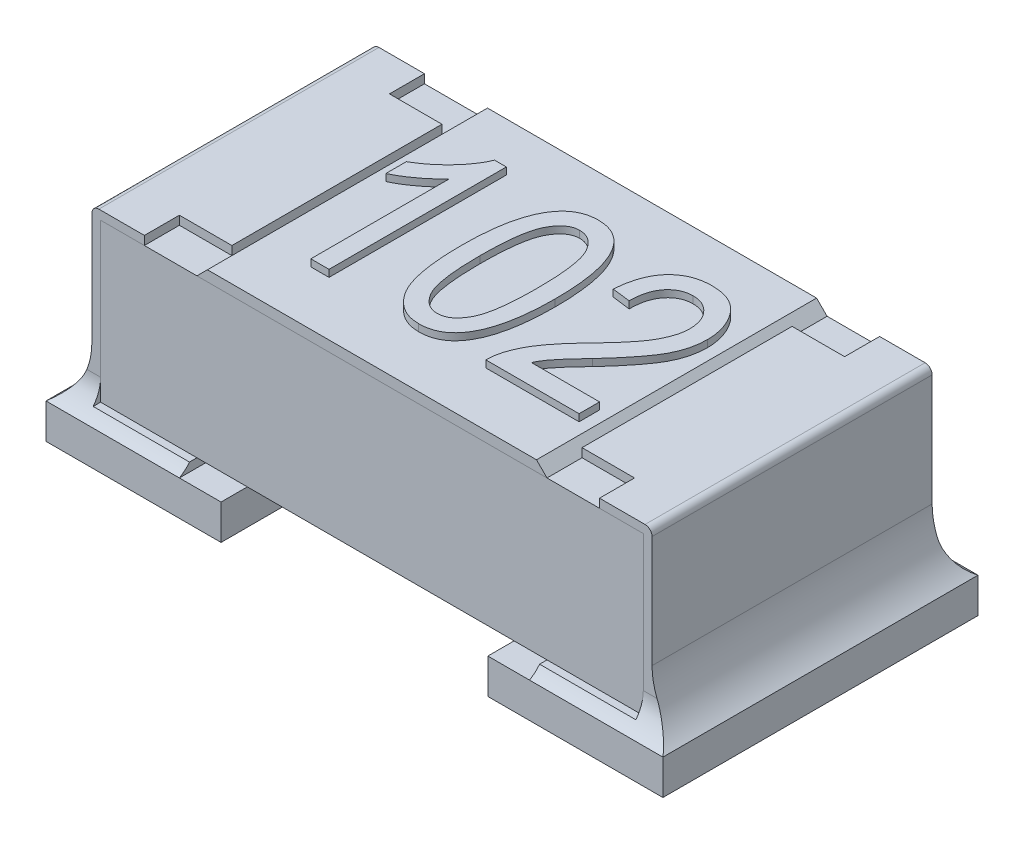
SolidWorks part; units mm, degrees
material "Ceramic Porcelain"
ref_plane "Front Plane" through (0, 0, 0) normal (0, 0, 1) x (1, 0, 0)
ref_plane "Top Plane" through (0, 0, 0) normal (0, 1, 0) x (1, 0, 0)
ref_plane "Right Plane" through (0, 0, 0) normal (1, 0, 0) x (0, 0, -1)
sketch "Sketch1" plane through (0, 0, 0) normal (1, 0, 0) x (0, 0, -1)
  line L0 (0, 55) -> (0, -55) construction
  line L1 (-0.4, 0.575) -> (0.4, 0.575)
  line L2 (-0.4, 0.575) -> (-0.4, 0.125)
  line L3 (-0.4, 0.125) -> (0.4, 0.125)
  line L4 (0.4, 0.575) -> (0.4, 0.125)
  line L5 (55, 0) -> (-55, 0) construction
  dimension "D1" = 0.8
  dimension "D2" = 0.4
  dimension "D3" = 0.45
  dimension "D4" = 0.125
extrude "Boss-Extrude1" add sketch "Sketch1" along normal mid plane 1.55
sketch "Sketch2" plane through (0, 0, 0) normal (0, 0, 1) x (1, 0, 0)
  line L0 (-0.5, 0.6) -> (-0.78, 0.6)
  line L1 (-0.8, 0.58) -> (-0.8, 0.1)
  line L2 (-0.8, 0.1) -> (-0.5, 0.1)
  line L3 (-0.5, 0.1) -> (-0.5, 0.125)
  line L4 (0.775, 0.125) -> (-0.775, 0.125) construction
  line L5 (-0.5, 0.125) -> (-0.775, 0.125)
  line L6 (-0.775, 0.125) -> (-0.775, 0.575)
  line L7 (-0.775, 0.575) -> (-0.5, 0.575)
  line L8 (0.775, 0.575) -> (-0.775, 0.575) construction
  line L9 (-0.5, 0.575) -> (-0.5, 0.6)
  line L11 (0.5, 0.575) -> (0.5, 0.6)
  line L12 (0.5, 0.6) -> (0.78, 0.6)
  line L13 (0.8, 0.58) -> (0.8, 0.1)
  line L14 (0.8, 0.1) -> (0.5, 0.1)
  line L15 (0.5, 0.1) -> (0.5, 0.125)
  line L16 (0.5, 0.125) -> (0.775, 0.125)
  line L17 (0.775, 0.125) -> (0.775, 0.575)
  line L18 (0.775, 0.575) -> (0.5, 0.575)
  arc A0 (0.78, 0.6) -> (0.8, 0.58) centre (0.78, 0.58) cw
  arc A1 (-0.78, 0.6) -> (-0.8, 0.58) centre (-0.78, 0.58) ccw
  point P28 (-0.8, 0.6)
  dimension "D6" = 0.02
  dimension "D1" = 0.025
  dimension "D2" = 0.025
  dimension "D3" = 0.025
  dimension "D4" = 0.3
  dimension "D5" = 0.3
extrude "Boss-Extrude2" add sketch "Sketch2" along normal mid plane 0.8 separate body
sketch "Sketch3" plane through (0, 0.6, 0) normal (0, 1, 0) x (1, 0, 0)
  line L0 (0.5, -0.4) -> (0.5, 0.4) construction
  line L1 (-0.5, 0.4) -> (-0.65, 0.4)
  line L2 (-0.5, 0.4) -> (-0.5, 0.3)
  line L3 (-0.5, 0.3) -> (-0.65, 0.3)
  line L4 (-0.65, 0.4) -> (-0.65, 0.3)
  line L5 (-0.5, -0.4) -> (-0.65, -0.4)
  line L6 (-0.5, -0.4) -> (-0.5, -0.3)
  line L7 (-0.5, -0.3) -> (-0.65, -0.3)
  line L8 (-0.65, -0.4) -> (-0.65, -0.3)
  line L9 (0.5, -0.4) -> (0.65, -0.4)
  line L10 (0.5, -0.4) -> (0.5, -0.3)
  line L11 (0.5, -0.3) -> (0.65, -0.3)
  line L12 (0.65, -0.4) -> (0.65, -0.3)
  line L13 (0.775, -0.4) -> (-0.775, -0.4) construction
  line L15 (0.5, 0.4) -> (0.65, 0.4)
  line L16 (0.5, 0.4) -> (0.5, 0.3)
  line L17 (0.5, 0.3) -> (0.65, 0.3)
  line L18 (0.65, 0.4) -> (0.65, 0.3)
  dimension "D1" = 0.15
  dimension "D2" = 0.1
extrude "Cut-Extrude1" cut sketch "Sketch3" against normal blind 0.025
sketch "Sketch4" plane through (0, 0, 0) normal (0, 0, 1) x (1, 0, 0)
  line L0 (-0.5, 0.575) -> (0.5, 0.575)
  line L1 (0.5, 0.575) -> (0.47, 0.605)
  line L2 (0.47, 0.605) -> (-0.47, 0.605)
  line L3 (-0.47, 0.605) -> (-0.5, 0.575)
  dimension "D1" = 45
  dimension "D2" = 45
  dimension "D3" = 0.03
extrude "Boss-Extrude3" add sketch "Sketch4" along normal mid plane 0.8 separate body
sketch "Sketch7" plane through (0, 0, 0) normal (0, 1, 0) x (1, 0, 0)
  line L0 (0, -0.2777) -> (0, 0.2777) construction
  line L1 (-0.381, -0.45) -> (-0.881, -0.45)
  line L2 (-0.381, -0.45) -> (-0.381, 0.45)
  line L3 (-0.381, 0.45) -> (-0.881, 0.45)
  line L4 (-0.881, -0.45) -> (-0.881, 0.45)
  line L5 (0.381, -0.45) -> (0.881, -0.45)
  line L6 (0.381, -0.45) -> (0.381, 0.45)
  line L7 (0.381, 0.45) -> (0.881, 0.45)
  line L8 (0.881, -0.45) -> (0.881, 0.45)
  line L9 (-0.2777, 0) -> (0.2777, 0) construction
  dimension "D1" = 0.5
  dimension "D2" = 0.381
  dimension "D3" = 0.381
  dimension "D4" = 0.9
  dimension "D5" = 0.45
extrude "Boss-Extrude5" add sketch "Sketch7" along normal blind 0.1
fillet "Fillet3" radius 0.2 1 edges at (-0.8, 0.1, 0)
fillet "Fillet4" radius 0.2 1 edges at (0.8, 0.1, 0)
fillet "Fillet5" radius 0.1 2 edges at (0.6905, 0.1, -0.4) (0.6905, 0.1, 0.4)
fillet "Fillet6" radius 0.1 2 edges at (-0.6905, 0.1, 0.4) (-0.6905, 0.1, -0.4)
sketch "Esquisse2" plane through (0, 0.605, 0) normal (0, 1, 0) x (1, 0, 0)
  text T0 "102" font "Arial Narrow" height 0.5
extrude "Boss.-Extru.1" add sketch "Esquisse2" along normal blind 0.02
